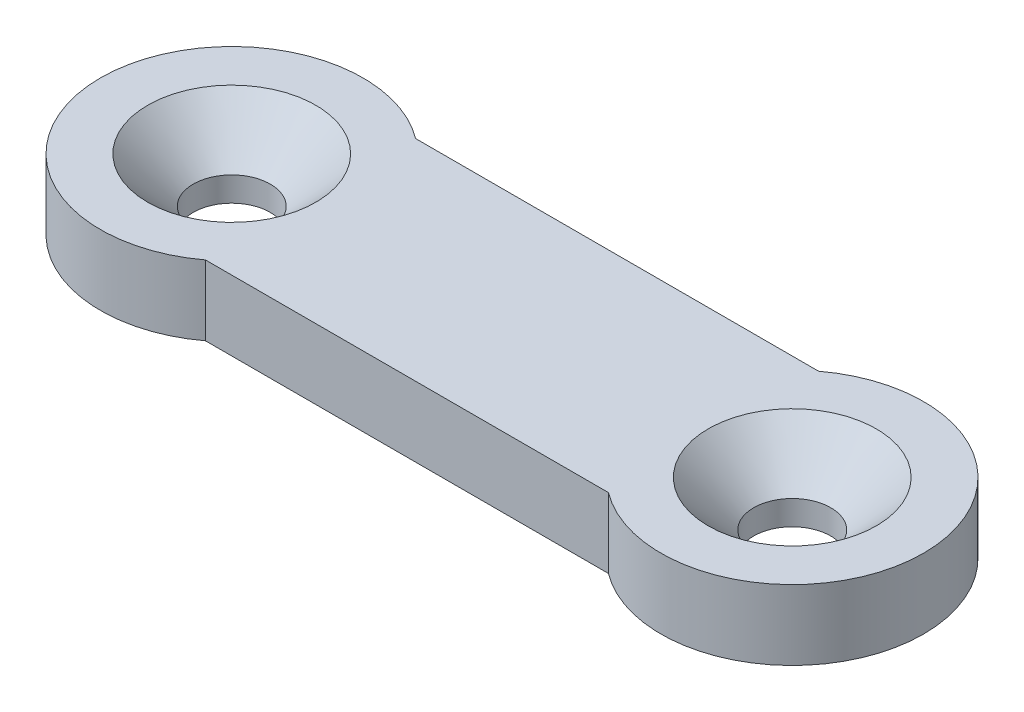
SolidWorks part; units mm, degrees
ref_plane "Front Plane" through (0, 0, 0) normal (0, 0, 1) x (1, 0, 0)
ref_plane "Top Plane" through (0, 0, 0) normal (0, 1, 0) x (1, 0, 0)
ref_plane "Right Plane" through (0, 0, 0) normal (1, 0, 0) x (0, 0, -1)
sketch "Sketch1" plane through (0, 0, 0) normal (0, 1, 0) x (1, 0, 0)
  line L0 (-8, 0) -> (8, 0) construction
  line L1 (-8, 3) -> (8, 3)
  line L2 (-8, -3) -> (8, -3)
  arc A0 (-8, 3) -> (-8, -3) centre (-8, 0) ccw
  arc A1 (8, -3) -> (8, 3) centre (8, 0) ccw
  circle A2 centre (-8, 0) radius 1.1
  circle A5 centre (8, 0) radius 1.1
  point P2 (0, 0)
  dimension "D1" = 2.2
  dimension "D2" = 16
  dimension "D3" = 6
extrude "Boss-Extrude1" add sketch "Sketch1" along normal blind 2
sketch "Sketch3" plane through (0, 2, 0) normal (0, 1, 0) x (1, 0, 0)
  circle A0 centre (-8, 0) radius 3.75
  circle A1 centre (8, 0) radius 3.75
  circle A2 centre (-8, 0) radius 1.1
  circle A3 centre (8, 0) radius 1.1
  circle A4 centre (-8, 0) radius 1.1 construction
  circle A5 centre (8, 0) radius 1.1 construction
  dimension "D1" = 7.5
extrude "Boss-Extrude3" add sketch "Sketch3" against normal up to surface (2 mm away) up to face at (0, 0, 0)
chamfer "Chamfer1" distance 1.3 angle 45 2 edges at (8, 2, 1.1) (-8, 2, 1.1)
sketch "Sketch2" plane through (0, 0, 0) normal (0, -1, 0) x (1, 0, 0)
  line L0 (-3.6, 0) -> (3.6, 0) construction
  line L1 (-5.75, 3) -> (5.75, 3) construction
  line L2 (-4.4, -3) -> (-3.6, -3)
  line L3 (-4.4, -3) -> (-4.4, 3)
  line L4 (-4.4, 3) -> (-3.6, 3)
  line L5 (-3.6, -3) -> (-3.6, 3)
  line L6 (4.4, -3) -> (3.6, -3)
  line L7 (4.4, -3) -> (4.4, 3)
  line L8 (4.4, 3) -> (3.6, 3)
  line L9 (3.6, -3) -> (3.6, 3)
  point P2 (0, 0)
  point P12 (-3.6, 0)
  point P17 (3.6, 0)
  dimension "D1" = 7.2
  dimension "D2" = 0.8
extrude "Boss-Extrude2" [suppressed] add sketch "Sketch2" along normal blind 4
